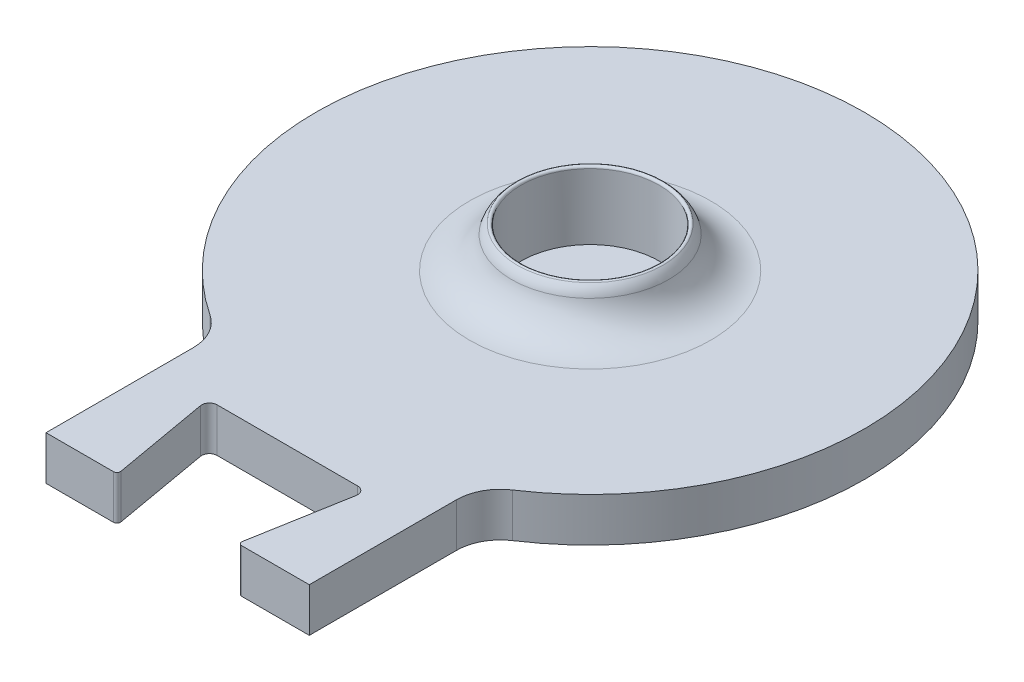
SolidWorks part; units mm, degrees
ref_plane "Front Plane" through (0, 0, 0) normal (0, 0, 1) x (1, 0, 0)
ref_plane "Top Plane" through (0, 0, 0) normal (0, 1, 0) x (1, 0, 0)
ref_plane "Right Plane" through (0, 0, 0) normal (1, 0, 0) x (0, 0, -1)
sketch "Sketch1" plane through (0, 0, 0) normal (0, 1, 0) x (1, 0, 0)
  line L0 (-6, 6) -> (-6, -13.2915)
  line L1 (-6, -19) -> (-2.7023, -19)
  line L2 (6, -19) -> (6, -13.2915)
  line L3 (6, 6) -> (-6, 6)
  line L4 (-6, -13.2915) -> (-6, -19)
  line L5 (6, -13.2915) -> (6, 6)
  line L6 (0, -19) -> (0, 0) construction
  line L7 (-2.6007, -19) -> (-3.5, -13.9) construction
  line L8 (-3.5, -13.9) -> (0, -13.9) construction
  line L9 (-2.7023, -19) -> (-3.6192, -13.8)
  line L10 (-3.6192, -13.8) -> (0, -13.8)
  line L11 (-2.6992, -19.0174) -> (-3.6192, -13.8) construction
  line L12 (2.7023, -19) -> (6, -19)
  line L13 (3.6192, -13.8) -> (0, -13.8)
  line L14 (2.7023, -19) -> (3.6192, -13.8)
  circle A0 centre (0, 0) radius 0.375 construction
  dimension "D1" = 0.75
  dimension "D5" = 6
  dimension "D7" = 80
  dimension "D2" = 25
  dimension "D3" = 6
  dimension "D4" = 12
  dimension "D8" = 3.5
  dimension "D9" = 5.1
  dimension "D10" = 0.1
extrude "Boss-Extrude1" add sketch "Sketch1" along normal blind 2
sketch "Sketch2" plane through (0, 0, 0) normal (0, 1, 0) x (1, 0, 0)
  circle A0 centre (0, 0) radius 12.5
  circle A1 centre (0, 0) radius 3
  dimension "D1" = 25
extrude "Boss-Extrude2" add sketch "Sketch2" along normal blind 2
sketch "Sketch3" plane through (0, 0, 0) normal (0, -1, 0) x (1, 0, 0)
  line L0 (-3, 0) -> (-3, 4)
  line L1 (3, 0) -> (3, 4)
  arc A0 (-3, 0) -> (3, 0) centre (0, 0) ccw
  arc A1 (-3, 4) -> (3, 4) centre (0, 0) ccw
extrude "Boss-Extrude3" [suppressed] add sketch "Sketch3" along normal blind 4
fillet "Fillet1" [suppressed] radius 0.5
fillet "Fillet2" [suppressed] radius 1
sketch "Sketch4" plane through (0, 2, 0) normal (0, 1, 0) x (1, 0, 0)
  line L0 (-6, -10.9659) -> (-6, -19) construction
  line L1 (-6, -18.8) -> (6, -18.8)
  line L2 (-6, -18.8) -> (-6, -19)
  line L3 (-6, -19) -> (6, -19)
  line L4 (6, -18.8) -> (6, -19)
  dimension "D1" = 0.2
extrude "Cut-Extrude1" cut sketch "Sketch4" against normal blind 4
fillet "Fillet3" radius 0.35 2 edges at (3.6192, 1, 13.8) (-3.6192, 1, 13.8)
fillet "Fillet4" radius 0.15 2 edges at (2.7375, 1, 18.8) (-2.7375, 1, 18.8)
sketch "Sketch5" plane through (0, 0, 0) normal (0, 1, 0) x (1, 0, 0)
  circle A1 centre (0, 0) radius 3
  circle A2 centre (0, 0) radius 2.1
  dimension "D1" = 4.2
  dimension "D2" = 6
extrude "Boss-Extrude4" [suppressed] add sketch "Sketch5" along normal blind 13
fillet "Fillet5" [suppressed] radius 2
fillet "Fillet6" radius 2 2 edges at (-6, 1, 10.9659) (6, 1, 10.9659)
sketch "Sketch6" plane through (0, 2, 0) normal (0, 1, 0) x (1, 0, 0)
  circle A0 centre (0, 0) radius 3.5
  dimension "D1" = 7
extrude "Boss-Extrude5" add sketch "Sketch6" along normal blind 2 contours A0
sketch "Sketch7" plane through (0, 4, 0) normal (0, 1, 0) x (1, 0, 0)
  circle A0 centre (0, 0) radius 3.15
extrude "Cut-Extrude3" cut sketch "Sketch7" against normal blind 3.2
fillet "Fillet7" radius 2 1 edges at (0, 2, 3.5)
fillet "Fillet8" radius 1 1 edges at (0, 4, 3.5)
fillet "Fillet9" radius 0.1 1 edges at (0, 4, 3.15)
sketch "Sketch8" plane through (0, 0.8, 0) normal (0, 1, 0) x (1, 0, 0)
  circle A0 centre (0, 0) radius 0.3
extrude "Cut-Extrude4" cut sketch "Sketch8" against normal through all
